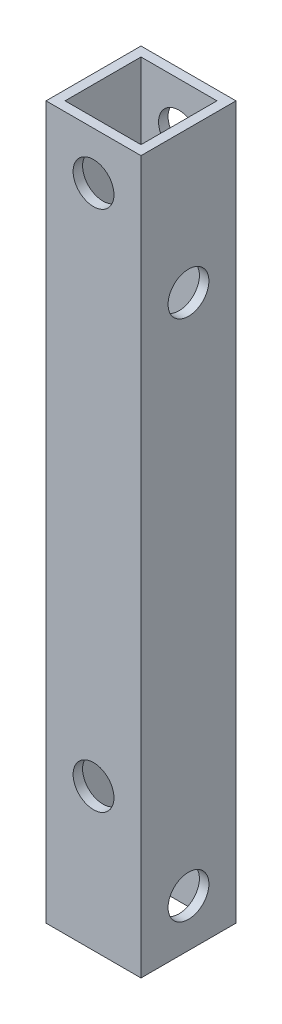
SolidWorks part; units mm, degrees
material "5052-H34"
ref_plane "正面" through (0, 0, 0) normal (0, 0, 1) x (1, 0, 0)
ref_plane "平面" through (0, 0, 0) normal (0, 1, 0) x (1, 0, 0)
ref_plane "右側面" through (0, 0, 0) normal (1, 0, 0) x (0, 0, -1)
sketch "ｽｹｯﾁ1" plane through (0, 0, 0) normal (0, 1, 0) x (1, 0, 0)
  line L1 (-5, 5) -> (5, 5)
  line L2 (-5, 5) -> (-5, -5)
  line L3 (-5, -5) -> (5, -5)
  line L4 (5, 5) -> (5, -5)
  line L5 (-5, 5) -> (5, -5) construction
  line L6 (-5, -5) -> (5, 5) construction
  point P0 (0, 0)
  dimension "D1" = 10
  dimension "D2" = 10
extrude "押し出し-薄板1" add sketch "ｽｹｯﾁ1" along normal blind 75 thin thin type one direction reverse wall 1
sketch "ｽｹｯﾁ2" plane through (5, 0, 0) normal (1, 0, 0) x (0, 0, -1)
  line L0 (0, 0) -> (0, 5) construction
  line L1 (0, 75) -> (0, 60) construction
  line L2 (-5, 75) -> (5, 75) construction
  circle A0 centre (0, 5) radius 2.15
  circle A1 centre (0, 60) radius 2.15
  dimension "D1" = 4.3
  dimension "D2" = 5
  dimension "D3" = 15
extrude "ｶｯﾄ - 押し出し1" cut sketch "ｽｹｯﾁ2" against normal through all
sketch "ｽｹｯﾁ3" plane through (0, 0, 5) normal (0, 0, 1) x (1, 0, 0)
  line L0 (0, 0) -> (0, 15) construction
  line L1 (0, 75) -> (0, 70) construction
  line L2 (-5, 75) -> (5, 75) construction
  circle A0 centre (0, 15) radius 2.15
  circle A1 centre (0, 70) radius 2.15
  dimension "D2" = 4.3
  dimension "D1" = 15
  dimension "D3" = 5
extrude "ｶｯﾄ - 押し出し2" cut sketch "ｽｹｯﾁ3" against normal through all
